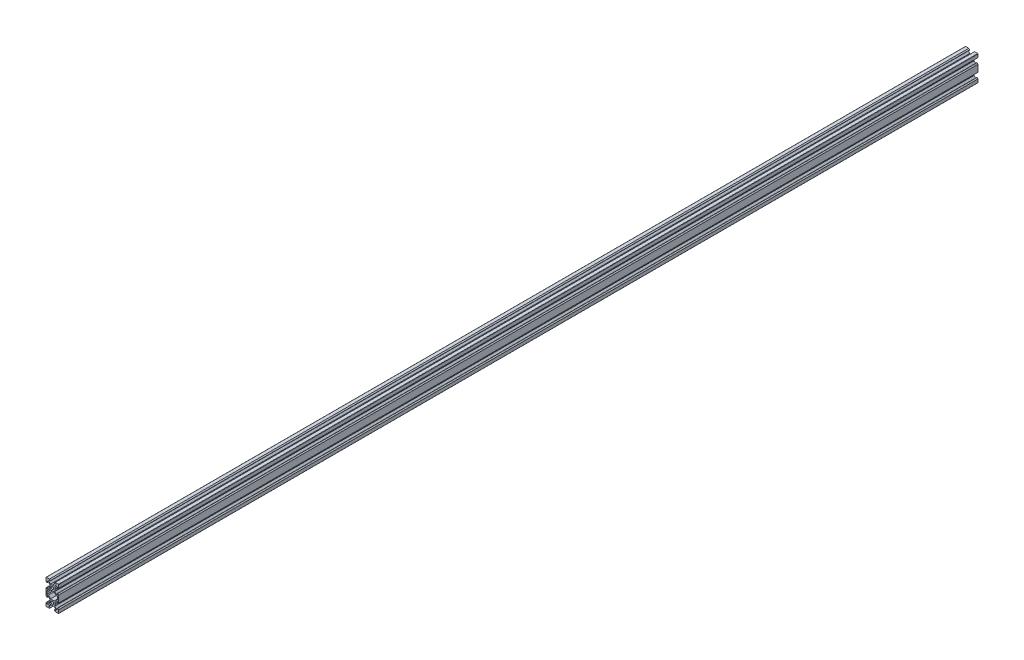
SolidWorks part; units mm, degrees
material "6061-T6 (SS)"
ref_plane "Front Plane" through (0, 0, 0) normal (0, 0, 1) x (1, 0, 0)
ref_plane "Top Plane" through (0, 0, 0) normal (0, 1, 0) x (1, 0, 0)
ref_plane "Right Plane" through (0, 0, 0) normal (1, 0, 0) x (0, 0, -1)
sketch "Sketch1" plane through (0, 0, 0) normal (0, 0, 1) x (1, 0, 0)
  line L0 (0, 0) -> (10, 0) construction
  line L1 (9.5, -20) -> (-9.5, -20)
  line L2 (10, -19.5) -> (10, 19.5)
  line L3 (9.5, 20) -> (-9.5, 20)
  line L4 (-10, -19.5) -> (-10, 19.5)
  line L5 (10, -20) -> (-10, 20) construction
  line L6 (10, 20) -> (-10, -20) construction
  circle A0 centre (0, 10) radius 2.1
  circle A1 centre (0, -10) radius 2.1
  arc A2 (-9.5, -20) -> (-10, -19.5) centre (-9.5, -19.5) cw
  arc A3 (9.5, -20) -> (10, -19.5) centre (9.5, -19.5) ccw
  arc A4 (10, 19.5) -> (9.5, 20) centre (9.5, 19.5) ccw
  arc A5 (-9.5, 20) -> (-10, 19.5) centre (-9.5, 19.5) ccw
  point P0 (0, 0)
  line B0 (0, 10) -> (0, 20) construction
  line B1 (0, 13.69) -> (-0.21, 13.9)
  line B2 (-0.21, 13.9) -> (-2.8393, 13.9)
  line B3 (-2.8393, 13.9) -> (-5.5, 16.5607)
  line B4 (-5.5, 16.5607) -> (-5.5, 18.2)
  line B5 (-5.5, 18.2) -> (-3.125, 18.2)
  line B6 (-3.125, 18.2) -> (-3.125, 18.545)
  line B7 (-3.125, 18.545) -> (-4.58, 20)
  line B8 (-4.58, 20) -> (4.58, 20)
  line B9 (0, 10) -> (-5.9132, 15.9132) construction
  line B10 (3.125, 18.545) -> (4.58, 20)
  line B11 (3.125, 18.2) -> (3.125, 18.545)
  line B12 (5.5, 18.2) -> (3.125, 18.2)
  line B13 (5.5, 16.5607) -> (5.5, 18.2)
  line B14 (2.8393, 13.9) -> (5.5, 16.5607)
  line B15 (0.21, 13.9) -> (2.8393, 13.9)
  line B16 (0, 13.69) -> (0.21, 13.9)
  line B17 (0, 10) -> (-10, 10) construction
  line B18 (-3.69, 10) -> (-3.9, 9.79)
  line B19 (-3.9, 9.79) -> (-3.9, 7.1607)
  line B20 (-3.9, 7.1607) -> (-6.5607, 4.5)
  line B21 (-6.5607, 4.5) -> (-8.2, 4.5)
  line B22 (-8.2, 4.5) -> (-8.2, 6.875)
  line B23 (-8.2, 6.875) -> (-8.545, 6.875)
  line B24 (-8.545, 6.875) -> (-10, 5.42)
  line B25 (-10, 5.42) -> (-10, 14.58)
  line B26 (0, 10) -> (-5.9132, 4.0868) construction
  line B27 (-8.545, 13.125) -> (-10, 14.58)
  line B28 (-8.2, 13.125) -> (-8.545, 13.125)
  line B29 (-8.2, 15.5) -> (-8.2, 13.125)
  line B30 (-6.5607, 15.5) -> (-8.2, 15.5)
  line B31 (-3.9, 12.8393) -> (-6.5607, 15.5)
  line B32 (-3.9, 10.21) -> (-3.9, 12.8393)
  line B33 (-3.69, 10) -> (-3.9, 10.21)
  line B34 (0, -10) -> (-10, -10) construction
  line B35 (-3.69, -10) -> (-3.9, -10.21)
  line B36 (-3.9, -10.21) -> (-3.9, -12.8393)
  line B37 (-3.9, -12.8393) -> (-6.5607, -15.5)
  line B38 (-6.5607, -15.5) -> (-8.2, -15.5)
  line B39 (-8.2, -15.5) -> (-8.2, -13.125)
  line B40 (-8.2, -13.125) -> (-8.545, -13.125)
  line B41 (-8.545, -13.125) -> (-10, -14.58)
  line B42 (-10, -14.58) -> (-10, -5.42)
  line B43 (0, -10) -> (-5.9132, -15.9132) construction
  line B44 (-8.545, -6.875) -> (-10, -5.42)
  line B45 (-8.2, -6.875) -> (-8.545, -6.875)
  line B46 (-8.2, -4.5) -> (-8.2, -6.875)
  line B47 (-6.5607, -4.5) -> (-8.2, -4.5)
  line B48 (-3.9, -7.1607) -> (-6.5607, -4.5)
  line B49 (-3.9, -9.79) -> (-3.9, -7.1607)
  line B50 (-3.69, -10) -> (-3.9, -9.79)
  line B51 (0, -10) -> (0, -20) construction
  line B52 (0, -13.69) -> (0.21, -13.9)
  line B53 (0.21, -13.9) -> (2.8393, -13.9)
  line B54 (2.8393, -13.9) -> (5.5, -16.5607)
  line B55 (5.5, -16.5607) -> (5.5, -18.2)
  line B56 (5.5, -18.2) -> (3.125, -18.2)
  line B57 (3.125, -18.2) -> (3.125, -18.545)
  line B58 (3.125, -18.545) -> (4.58, -20)
  line B59 (4.58, -20) -> (-4.58, -20)
  line B60 (0, -10) -> (5.9132, -15.9132) construction
  line B61 (-3.125, -18.545) -> (-4.58, -20)
  line B62 (-3.125, -18.2) -> (-3.125, -18.545)
  line B63 (-5.5, -18.2) -> (-3.125, -18.2)
  line B64 (-5.5, -16.5607) -> (-5.5, -18.2)
  line B65 (-2.8393, -13.9) -> (-5.5, -16.5607)
  line B66 (-0.21, -13.9) -> (-2.8393, -13.9)
  line B67 (0, -13.69) -> (-0.21, -13.9)
  line B68 (0, -10) -> (10, -10) construction
  line B69 (3.69, -10) -> (3.9, -9.79)
  line B70 (3.9, -9.79) -> (3.9, -7.1607)
  line B71 (3.9, -7.1607) -> (6.5607, -4.5)
  line B72 (6.5607, -4.5) -> (8.2, -4.5)
  line B73 (8.2, -4.5) -> (8.2, -6.875)
  line B74 (8.2, -6.875) -> (8.545, -6.875)
  line B75 (8.545, -6.875) -> (10, -5.42)
  line B76 (10, -5.42) -> (10, -14.58)
  line B77 (0, -10) -> (5.9132, -4.0868) construction
  line B78 (8.545, -13.125) -> (10, -14.58)
  line B79 (8.2, -13.125) -> (8.545, -13.125)
  line B80 (8.2, -15.5) -> (8.2, -13.125)
  line B81 (6.5607, -15.5) -> (8.2, -15.5)
  line B82 (3.9, -12.8393) -> (6.5607, -15.5)
  line B83 (3.9, -10.21) -> (3.9, -12.8393)
  line B84 (3.69, -10) -> (3.9, -10.21)
  line B85 (0, 10) -> (10, 10) construction
  line B86 (3.69, 10) -> (3.9, 10.21)
  line B87 (3.9, 10.21) -> (3.9, 12.8393)
  line B88 (3.9, 12.8393) -> (6.5607, 15.5)
  line B89 (6.5607, 15.5) -> (8.2, 15.5)
  line B90 (8.2, 15.5) -> (8.2, 13.125)
  line B91 (8.2, 13.125) -> (8.545, 13.125)
  line B92 (8.545, 13.125) -> (10, 14.58)
  line B93 (10, 14.58) -> (10, 5.42)
  line B94 (0, 10) -> (5.9132, 15.9132) construction
  line B95 (8.545, 6.875) -> (10, 5.42)
  line B96 (8.2, 6.875) -> (8.545, 6.875)
  line B97 (8.2, 4.5) -> (8.2, 6.875)
  line B98 (6.5607, 4.5) -> (8.2, 4.5)
  line B99 (3.9, 7.1607) -> (6.5607, 4.5)
  line B100 (3.9, 9.79) -> (3.9, 7.1607)
  line B101 (3.69, 10) -> (3.9, 9.79)
  line B102 (-8.2, -2.7) -> (-8.2, 2.7)
  line B103 (-8.2, 2.7) -> (-6.2393, 2.7)
  line B104 (-6.2393, 2.7) -> (-2.8393, 6.1)
  line B105 (-2.8393, 6.1) -> (2.8393, 6.1)
  line B106 (0, 6.1) -> (0, 0) construction
  line B107 (0, 0) -> (-8.2, 0) construction
  line B108 (6.2393, 2.7) -> (2.8393, 6.1)
  line B109 (8.2, 2.7) -> (6.2393, 2.7)
  line B110 (8.2, -2.7) -> (8.2, 2.7)
  line B111 (8.2, -2.7) -> (6.2393, -2.7)
  line B112 (6.2393, -2.7) -> (2.8393, -6.1)
  line B113 (-2.8393, -6.1) -> (2.8393, -6.1)
  line B114 (-6.2393, -2.7) -> (-2.8393, -6.1)
  line B115 (-8.2, -2.7) -> (-6.2393, -2.7)
  line B116 (0, 6.1) -> (0, 10) construction
  line B117 (0, 10) -> (-5.0927, 4.9073) construction
  dimension "D4" = 4.2
  dimension "D5" = 0.5
  dimension "D1" = 20
  dimension "D2" = 40
  dimension "D3" = 20
sketch_block_instance "V Slot 1-4"
sketch_block "V Slot 1" parameters "D1"=10, "D2"=11, "D3"=4.3, "D4"=1.8, "D5"=0.21, "D6"=45, "D7"=9.16, "D8"=1.5, "D9"=6.25
sketch_block_instance "V Slot 1-5"
sketch_block_instance "V Slot 1-6"
sketch_block_instance "V Slot 1-7"
sketch_block_instance "V Slot 1-8"
sketch_block_instance "V Slot 1-9"
sketch_block_instance "Center Cutout 1-1"
sketch_block "Center Cutout 1" parameters "D1"=5.4, "D2"=12.2, "D3"=8.2, "D4"=45, "D5"=10, "D6"=1.5
extrude "Boss-Extrude1" add sketch "Sketch1" along normal blind 1447.8 contours B101 B86 B87 B88 B89 B90 B91 B92 L2 A4 L3 B10 B11 B12 B13 B14 B15 B16 B1 B2 B3 B4 B5 B6 B7 A5 L4 B27 B28 B29 B30 B31 B32 B33 B18 B19 B20 B21 B22 B23 B24 B44 B45 B46 B47 B48 B49 B50 B35 region at (7.04, -19.5528, 0)
